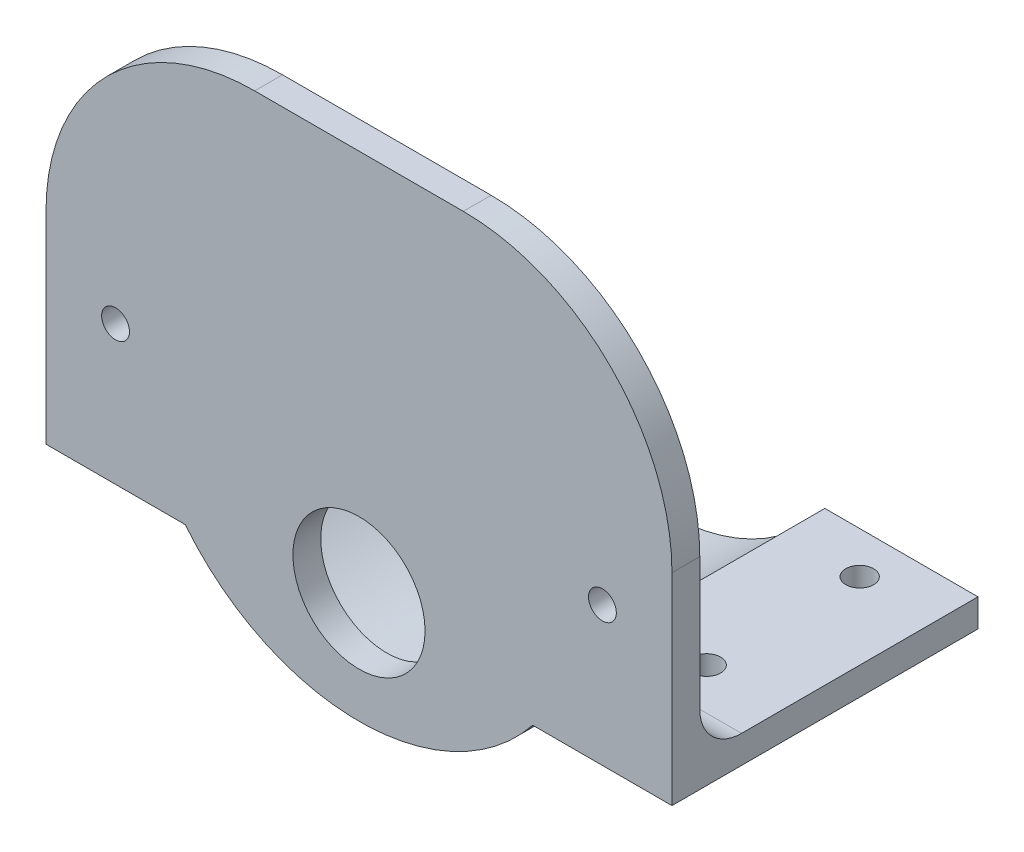
SolidWorks part; units mm, degrees
ref_plane "Front Plane" through (0, 0, 0) normal (0, 0, 1) x (1, 0, 0)
ref_plane "Top Plane" through (0, 0, 0) normal (0, 1, 0) x (1, 0, 0)
ref_plane "Right Plane" through (0, 0, 0) normal (1, 0, 0) x (0, 0, -1)
sketch "Sketch1" plane through (0, 0, 0) normal (0, 0, 1) x (1, 0, 0)
  line L0 (-17.5, 0) -> (17.5, 0) construction
  line L1 (0, 0) -> (0, -8) construction
  line L2 (0, 0) -> (0, 2) construction
  line L3 (-22.5, -8) -> (22.5, -8)
  line L4 (-22.5, 19.5) -> (22.5, 19.5)
  line L5 (-22.5, 19.5) -> (-22.5, -15.5)
  line L6 (-22.5, -15.5) -> (22.5, -15.5)
  line L7 (22.5, 19.5) -> (22.5, -15.5)
  line L8 (-22.5, 19.5) -> (22.5, -15.5) construction
  line L9 (-22.5, -15.5) -> (22.5, 19.5) construction
  circle A0 centre (0, 0) radius 14
  circle A1 centre (17.5, 0) radius 1
  circle A2 centre (-17.5, 0) radius 1
  circle A3 centre (0, -8) radius 4.75
  point P6 (0, 0)
  point P18 (0, -8)
extrude "Boss-Extrude2" add sketch "Sketch1" along normal blind 2 contours A0 L3 L7 L4 L5 A2 A1 | A3 L3 A0 | A3 L3 A0 region at (-21.9726, 5.75, 0) region at (0, 2.5294, 0) region at (-8.1196, -8.2375, 0)
sketch "Sketch2" plane through (0, 0, 2) normal (0, 0, 1) x (1, 0, 0)
  line L0 (-22.5, -8) -> (-22.5, -10)
  line L1 (22.5, -8) -> (22.5, -10)
  line L7 (12.49, -10) -> (22.5, -10)
  line L8 (-22.5, -10) -> (-12.49, -10)
  line L9 (12.49, -10) -> (22.5, -10)
  line L10 (-22.5, -10) -> (-12.49, -10)
  line L14 (11.4891, -8) -> (22.5, -8)
  line L15 (22.5, -8) -> (22.5, 19.5)
  line L16 (22.5, 19.5) -> (-22.5, 19.5)
  line L17 (-22.5, 19.5) -> (-22.5, -8)
  line L18 (-22.5, -8) -> (-11.4891, -8)
  line L19 (11.4891, -8) -> (22.5, -8)
  line L23 (-22.5, -8) -> (-11.4891, -8)
  arc A4 (-12.49, -10) -> (12.49, -10) centre (0, 0) ccw
  arc A5 (-12.49, -10) -> (12.49, -10) centre (0, 0) ccw
  arc A6 (-11.4891, -8) -> (11.4891, -8) centre (0, 0) ccw
  arc A7 (-11.4891, -8) -> (11.4891, -8) centre (0, 0) ccw
  dimension "D1" = 2
  dimension "D2" = 0
extrude "Boss-Extrude3" add sketch "Sketch2" against normal blind 22
fillet "Fillet1" radius 15 2 edges at (22.5, 19.5, 1) (-22.5, 19.5, 1)
fillet "Fillet2" radius 3 2 edges at (16.9946, -8, 0) (-16.9946, -8, 0)
sketch "Sketch3" plane through (0, -8, 0) normal (0, 1, 0) x (1, 0, 0)
  line L0 (-11.4891, 20) -> (-22.5, 20) construction
  line L1 (22.5, 20) -> (11.4891, 20) construction
  circle A0 centre (-16.9946, 6) radius 1
  circle A1 centre (-16.9946, 17) radius 1
  circle A2 centre (16.9946, 17) radius 1
  circle A3 centre (16.9946, 6) radius 1
  dimension "D1" = 3
  dimension "D3" = 3
  dimension "D2" = 14
  dimension "D4" = 14
extrude "Cut-Extrude1" cut sketch "Sketch3" against normal blind 21
